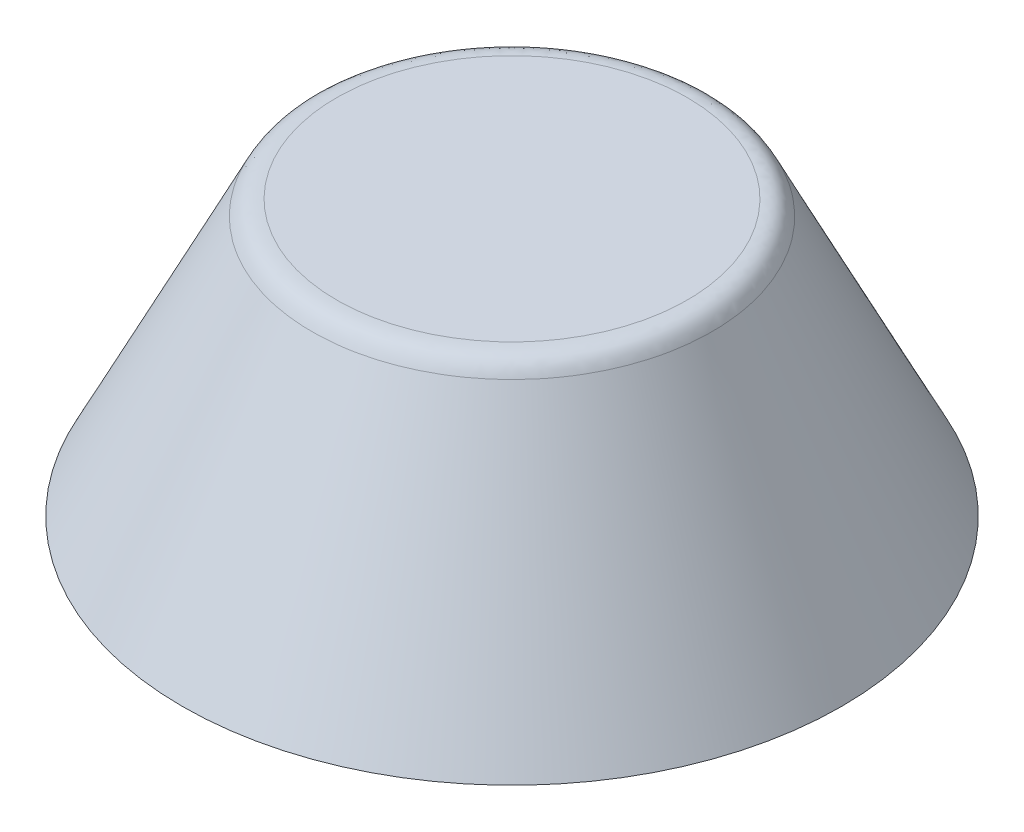
SolidWorks part; units mm, degrees
ref_plane "Front Plane" through (0, 0, 0) normal (0, 0, 1) x (1, 0, 0)
ref_plane "Top Plane" through (0, 0, 0) normal (0, 1, 0) x (1, 0, 0)
ref_plane "Right Plane" through (0, 0, 0) normal (1, 0, 0) x (0, 0, -1)
sketch "Sketch1" plane through (0, 0, 0) normal (0, 0, 1) x (1, 0, 0)
  line L0 (0, 0) -> (0, 5) construction
  line L1 (0, 5) -> (3.5, 5)
  line L2 (3.5, 5) -> (6, 0)
  line L3 (6, 0) -> (0, 0) construction
  line L4 (0, 4) -> (0, 5)
  line L5 (0, 0) -> (2.75, 0) construction
  line L6 (0, 0) -> (0, 4) construction
  line L7 (0, 4) -> (2.75, 4)
  line L8 (2.75, 0) -> (2.75, 4)
  line L9 (2.75, 0) -> (6, 0)
  dimension "D1" = 6
  dimension "D2" = 3.5
  dimension "D3" = 5
  dimension "D4" = 2.75
  dimension "D5" = 1
revolve "Revolve1" add sketch "Sketch1" angle 360 about L0
fillet "Fillet1" radius 0.5 1 edges at (0, 5, -3.5) curvature continuous yes second distance 0.5 first distance on face at (0, 5, -3.5)
fillet "Fillet2" radius 0.5 1 edges at (0, 0, -2.75) curvature continuous yes second distance 0.5 first distance on face at (0, 0, -6)
